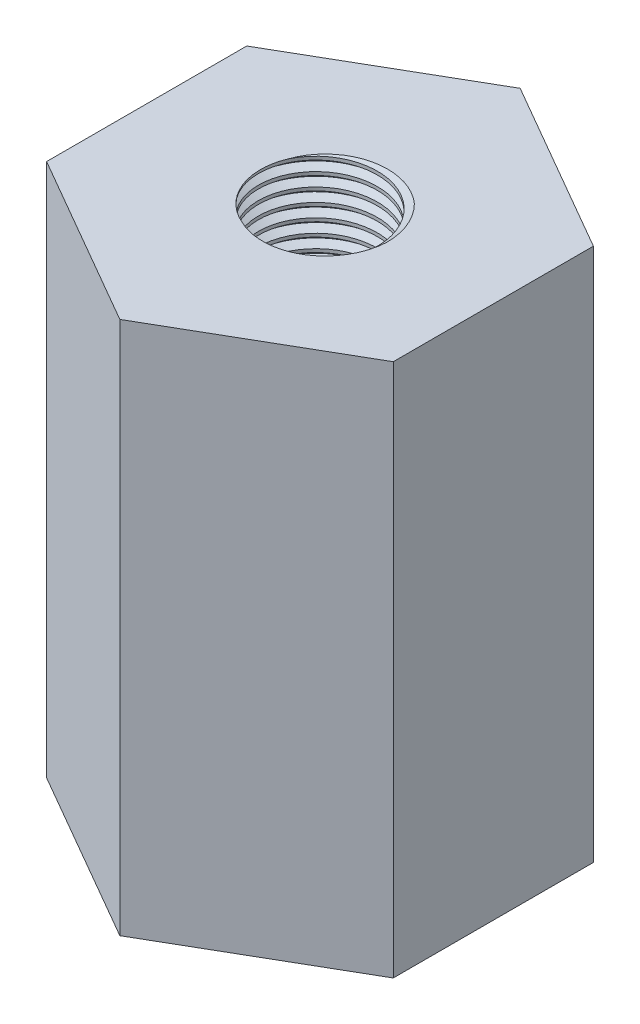
SolidWorks part; units mm, degrees
ref_plane "Front Plane" through (0, 0, 0) normal (0, 0, 1) x (1, 0, 0)
ref_plane "Top Plane" through (0, 0, 0) normal (0, 1, 0) x (1, 0, 0)
ref_plane "Right Plane" through (0, 0, 0) normal (1, 0, 0) x (0, 0, -1)
sketch "Sketch2" plane through (0, 0, 0) normal (0, 1, 0) x (1, 0, 0)
  line L1 (0, 15) -> (-12.9904, 7.5)
  line L2 (-12.9904, 7.5) -> (-12.9904, -7.5)
  line L3 (-12.9904, -7.5) -> (0, -15)
  line L4 (0, -15) -> (12.9904, -7.5)
  line L5 (12.9904, -7.5) -> (12.9904, 7.5)
  line L6 (12.9904, 7.5) -> (0, 15)
  circle A0 centre (0, 0) radius 12.9904 construction
  dimension "D1" = 15
extrude "Boss-Extrude1" add sketch "Sketch2" against normal blind 40
sketch "Sketch3" plane through (0, 0, 0) normal (0, 1, 0) x (1, 0, 0)
  circle A0 centre (0, 0) radius 5
  dimension "D1" = 10
extrude "Cut-Extrude1" cut sketch "Sketch3" against normal blind 30
thread "Thread1" pitch 1 start angle 0, offset 0, length 0, pitch 1, diameter 10
ref_plane "Plane1" through (5, -30, 0) normal (0, 0, 1) x (1, 0, 0)
sketch "Thread Profile1" plane through (5, -30, 0) normal (0, 0, 1) x (1, 0, 0)
  line L0 (0, 0) -> (0, 1) construction
  line L11 (0, 0) -> (0, 0.875)
  line L12 (0, 0.875) -> (-0.5413, 0.5625)
  line L13 (-0.5413, 0.5625) -> (-0.5413, 0.3125)
  line L15 (-0.5413, 0.3125) -> (0, 0)
  line L17 (-0.5413, 0.4375) -> (0, 0.4375) construction
  point P2 (0, 0)
  dimension "Pitch" = 1
  dimension "Profile_Angle" = 60
  dimension "Profile_Land" = 0.25
  dimension "Profile_Height" = 0.5413
ref_plane "Plane2" through (0, 0, 0) normal (0, 1, 0) x (1, 0, 0)
other "SurfaceCut1"
